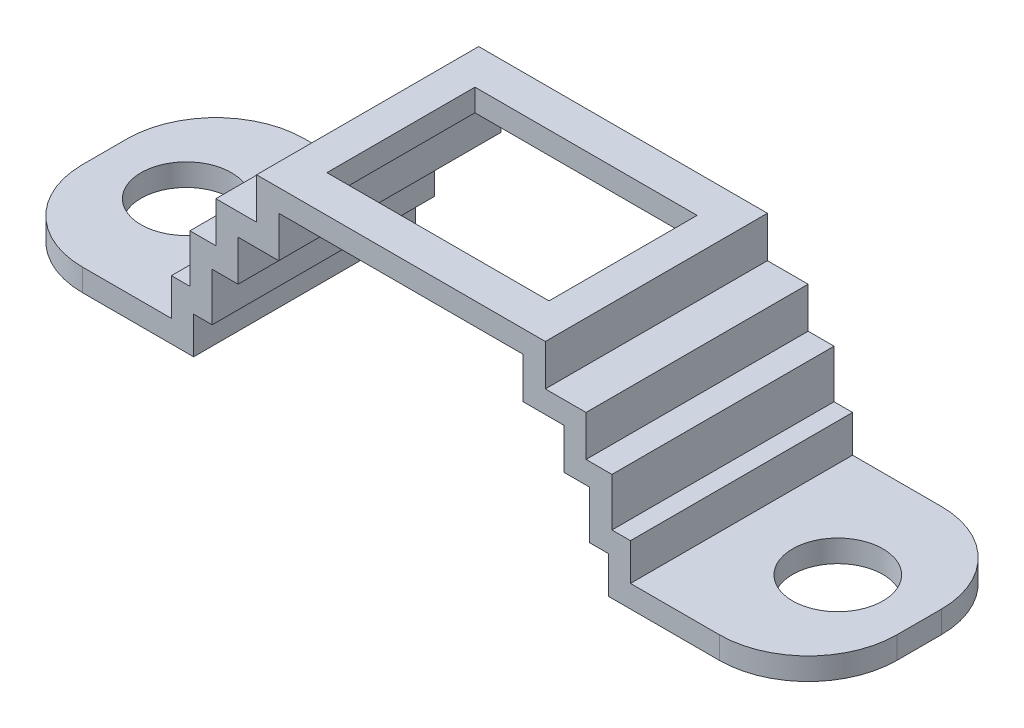
SolidWorks part; units mm, degrees
ref_plane "Front Plane" through (0, 0, 0) normal (0, 0, 1) x (1, 0, 0)
ref_plane "Top Plane" through (0, 0, 0) normal (0, 1, 0) x (1, 0, 0)
ref_plane "Right Plane" through (0, 0, 0) normal (1, 0, 0) x (0, 0, -1)
sketch "Sketch1" plane through (0, 0, 0) normal (0, 0, 1) x (1, 0, 0)
  line L0 (-55, 4.5) -> (-28, 4.5)
  line L1 (-28, 4.5) -> (-28, 9.5)
  line L2 (-28, 9.5) -> (-25.5, 9.5)
  line L3 (-25.5, 9.5) -> (-25.5, 16)
  line L4 (-25.5, 16) -> (-22, 16)
  line L5 (-22, 16) -> (-22, 21.5)
  line L6 (-22, 21.5) -> (-16.5, 21.5)
  line L7 (-16.5, 21.5) -> (-16.5, 27.05)
  line L8 (-16.5, 27.05) -> (0, 27.05)
  circle A0 centre (0, 0) radius 27.05
  dimension "D1" = 54.1
  dimension "D2" = 27
  dimension "D3" = 4.5
  dimension "D4" = 28
  dimension "D5" = 5
  dimension "D6" = 2.5
  dimension "D7" = 6.5
  dimension "D8" = 3.5
  dimension "D9" = 5.5
  dimension "D10" = 5.5
  dimension "D11" = 16.5
  dimension "D12" = 5.55
extrude "Extrude-Thin1" add sketch "Sketch1" along normal mid plane 30 thin contours L0 L1 L2 L3 L4 L5 L6 L7 L8 thin type one direction reverse wall 3
sketch "Sketch2" plane through (0, 7.5, 0) normal (0, 1, 0) x (1, 0, 0)
  line L0 (0, -15) -> (0, 15) construction
  circle A0 centre (-44, 0) radius 6.1
  dimension "D1" = 12.2
  dimension "D2" = 44
extrude "Cut-Extrude1" cut sketch "Sketch2" against normal through all
fillet "Fillet1" radius 12 2 edges at (-55, 6, -15) (-55, 6, 15)
mirror "Mirror1" about plane through (0, 30.05, 15) normal (1, 0, 0) of "Fillet1", "Cut-Extrude1", "Extrude-Thin1"
sketch "Sketch3" plane through (0, 30.05, 0) normal (0, 1, 0) x (1, 0, 0)
  line L1 (15, -10) -> (-15, -10)
  line L2 (15, -10) -> (15, 10)
  line L3 (15, 10) -> (-15, 10)
  line L4 (-15, -10) -> (-15, 10)
  line L5 (15, -10) -> (-15, 10) construction
  line L6 (15, 10) -> (-15, -10) construction
  point P0 (0, 0)
  dimension "D1" = 30
  dimension "D2" = 20
extrude "Cut-Extrude2" cut sketch "Sketch3" against normal through all
